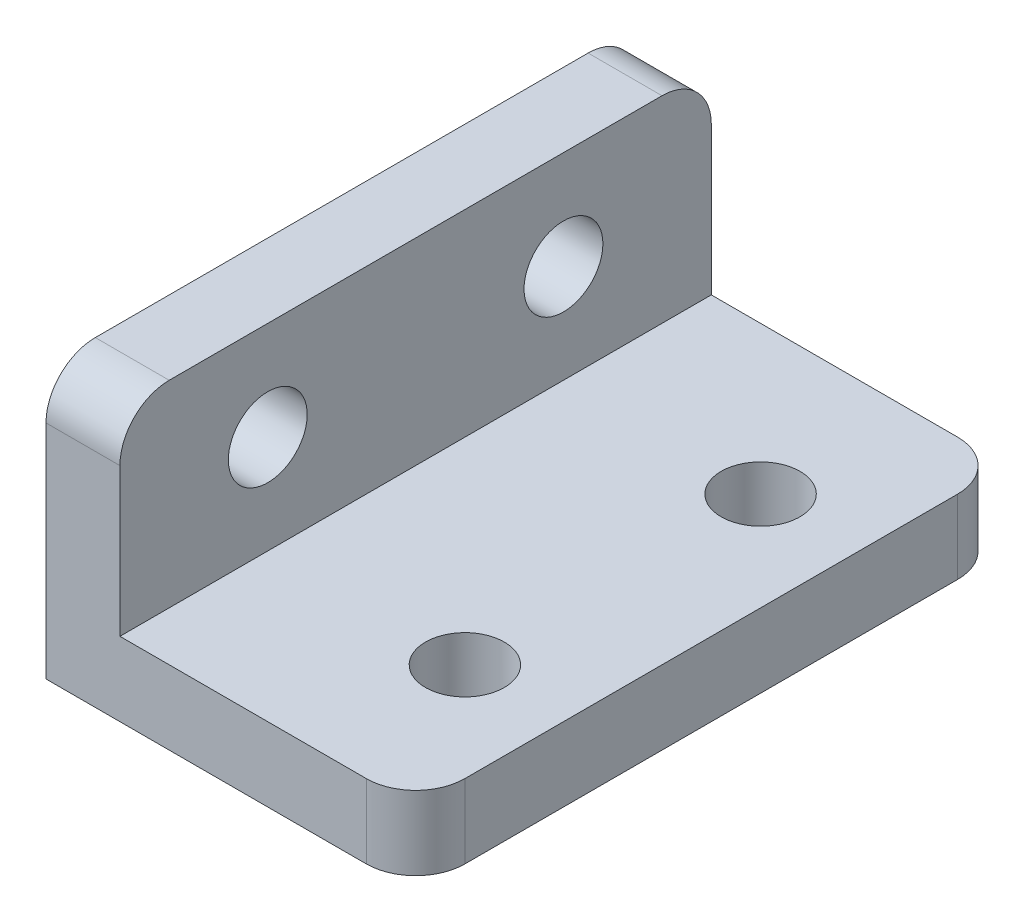
SolidWorks part; units mm, degrees
ref_plane "前视基准面" through (0, 0, 0) normal (0, 0, 1) x (1, 0, 0)
ref_plane "上视基准面" through (0, 0, 0) normal (0, 1, 0) x (1, 0, 0)
ref_plane "右视基准面" through (0, 0, 0) normal (1, 0, 0) x (0, 0, -1)
sketch "草图1" plane through (0, 0, 0) normal (0, 0, 1) x (1, 0, 0)
  line L0 (3, 231.6916) -> (3, 101.6916) construction
  line L1 (3, 112.6916) -> (6, 112.6916)
  line L2 (3, 112.6916) -> (3, -64.3846)
  line L4 (6, 112.6916) -> (6, 104.6916)
  line L6 (3, 101.6916) -> (18, 101.6916)
  line L7 (3, 101.6916) -> (3, -61.5122)
  line L8 (6, 104.6916) -> (18, 104.6916)
  line L9 (18, 101.6916) -> (18, 104.6916)
  dimension "D1" = 3
  dimension "D2" = 3
  dimension "D3" = 8
  dimension "D4" = 12
extrude "凸台-拉伸1" add sketch "草图1" against normal blind 24 contours L6 L9 L8 L4 L1 L2 L7 region at (4.5, 112.5056, 0)
sketch "草图2" plane through (6, 0, 0) normal (1, 0, 0) x (0, 0, -1)
  line L0 (24, 112.6916) -> (0, 112.6916) construction
  line L1 (0, 112.6916) -> (0, 104.6916) construction
  line L2 (24, 112.6916) -> (24, 104.6916) construction
  circle A0 centre (6, 108.6916) radius 1.6
  circle A1 centre (18, 108.6916) radius 1.6
  dimension "D1" = 3.2
  dimension "D2" = 3.2
  dimension "D3" = 4
  dimension "D4" = 6
  dimension "D5" = 6
  dimension "D6" = 4
extrude "切除-拉伸1" cut sketch "草图2" against normal blind 24
sketch "草图3" plane through (0, 104.6916, 0) normal (0, 1, 0) x (1, 0, 0)
  line L0 (18, 24) -> (18, 0) construction
  line L1 (6, 0) -> (18, 0) construction
  line L2 (6, 24) -> (18, 24) construction
  circle A0 centre (14, 6) radius 1.6
  circle A1 centre (14, 18) radius 1.6
  dimension "D1" = 3.2
  dimension "D2" = 3.2
  dimension "D3" = 4
  dimension "D4" = 4
  dimension "D5" = 6
  dimension "D6" = 6
extrude "切除-拉伸2" cut sketch "草图3" against normal blind 24
fillet "圆角1" radius 2 4 edges at (18, 103.1916, -24) (18, 103.1916, 0) (4.5, 112.6916, -24) (4.5, 112.6916, 0)
